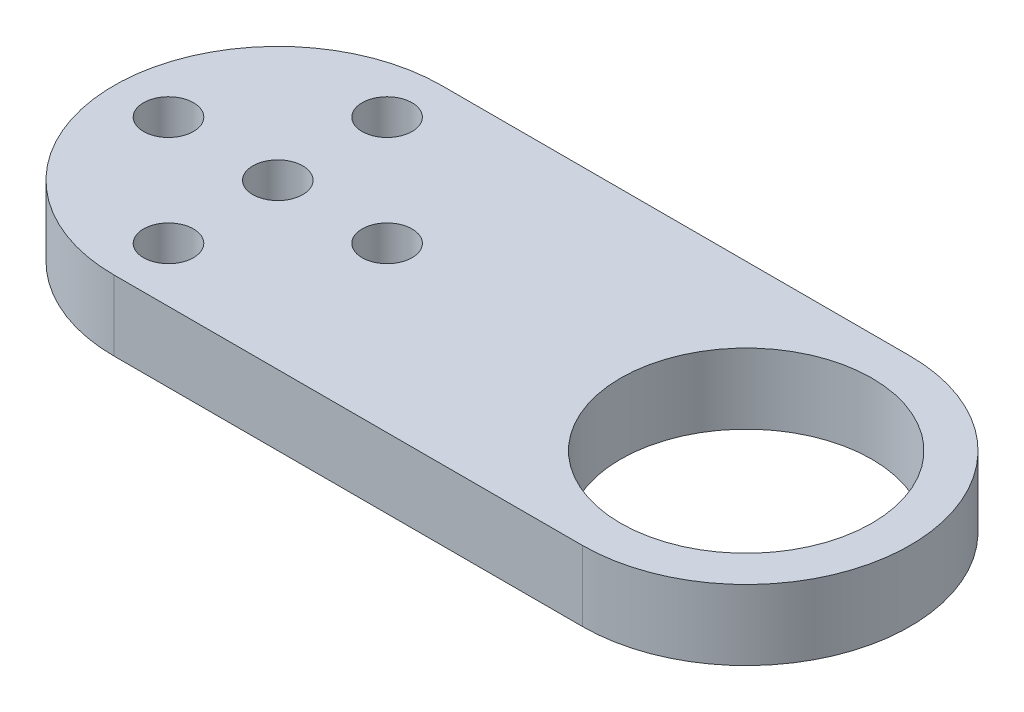
SolidWorks part; units mm, degrees
ref_plane "Front Plane" through (0, 0, 0) normal (0, 0, 1) x (1, 0, 0)
ref_plane "Top Plane" through (0, 0, 0) normal (0, 1, 0) x (1, 0, 0)
ref_plane "Right Plane" through (0, 0, 0) normal (1, 0, 0) x (0, 0, -1)
sketch "Sketch2" plane through (0, 0, 0) normal (0, 1, 0) x (1, 0, 0)
  line L0 (15, 0) -> (-15, 0) construction
  line L1 (15, 10.5) -> (-15, 10.5)
  line L2 (15, -10.5) -> (-15, -10.5)
  arc A0 (15, 10.5) -> (15, -10.5) centre (15, 0) cw
  arc A1 (-15, 10.5) -> (-15, -10.5) centre (-15, 0) ccw
  point P4 (0, 0)
  dimension "D1" = 30
  dimension "D2" = 10.5
  dimension "D3" = 10.5
extrude "Boss-Extrude1" add sketch "Sketch2" along normal blind 4.5
sketch "Sketch4" plane through (0, 4.5, 0) normal (0, 1, 0) x (1, 0, 0)
  line L0 (-15, 0) -> (-8, 0) construction
  line L1 (15, 0) -> (-15, 0) construction
  line L2 (-15, 0) -> (-8, 0) construction
  circle A0 centre (-15, 0) radius 1.6
  circle A1 centre (-8, 0) radius 1.6
  circle A2 centre (-15, -7) radius 1.6
  circle A3 centre (-22, 0) radius 1.6
  circle A4 centre (-15, 7) radius 1.6
  dimension "D1" = 3.2
  dimension "D2" = 7
  dimension "D3" = 4
extrude "Servo horn holes" cut sketch "Sketch4" against normal through all
sketch "Sketch5" plane through (0, 0, 0) normal (0, -1, 0) x (-1, 0, 0)
  circle A0 centre (-15, 0) radius 8.05
  dimension "D1" = 16.1
extrude "Bearing press fit" cut sketch "Sketch5" against normal through all
